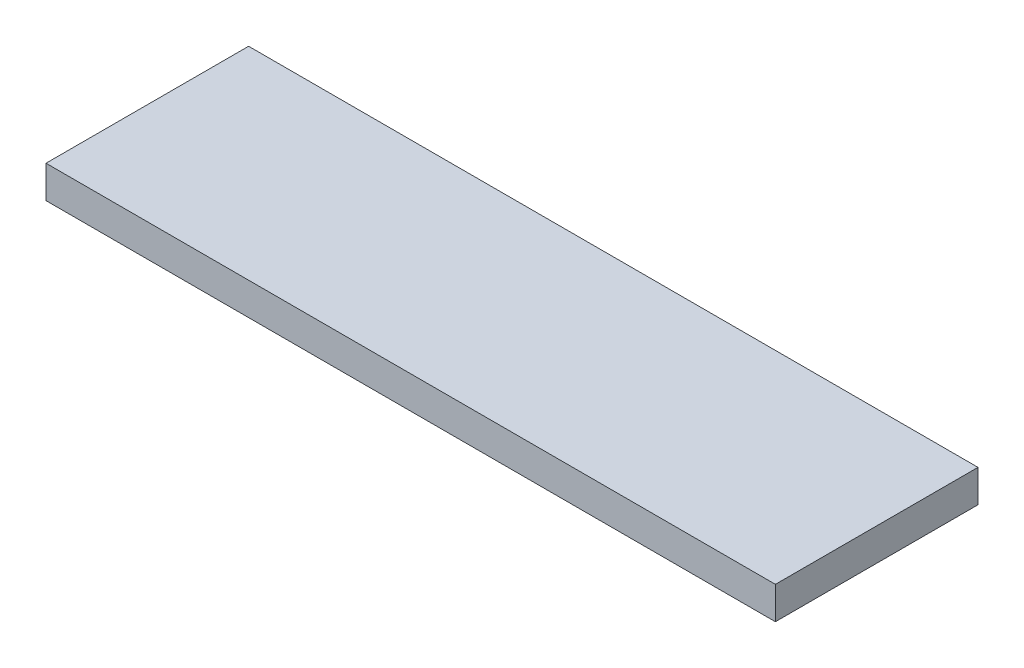
SolidWorks part; units mm, degrees
ref_plane "Front Plane" through (0, 0, 0) normal (0, 0, 1) x (1, 0, 0)
ref_plane "Top Plane" through (0, 0, 0) normal (0, 1, 0) x (1, 0, 0)
ref_plane "Right Plane" through (0, 0, 0) normal (1, 0, 0) x (0, 0, -1)
sketch "Sketch1" plane through (0, 0, 0) normal (0, 1, 0) x (1, 0, 0)
  line L1 (0, 0) -> (45, 0)
  line L2 (0, 0) -> (0, 12.5)
  line L3 (0, 12.5) -> (45, 12.5)
  line L4 (45, 0) -> (45, 12.5)
  dimension "D1" = 12.5
  dimension "D2" = 45
extrude "Boss-Extrude1" add sketch "Sketch1" along normal blind 2
